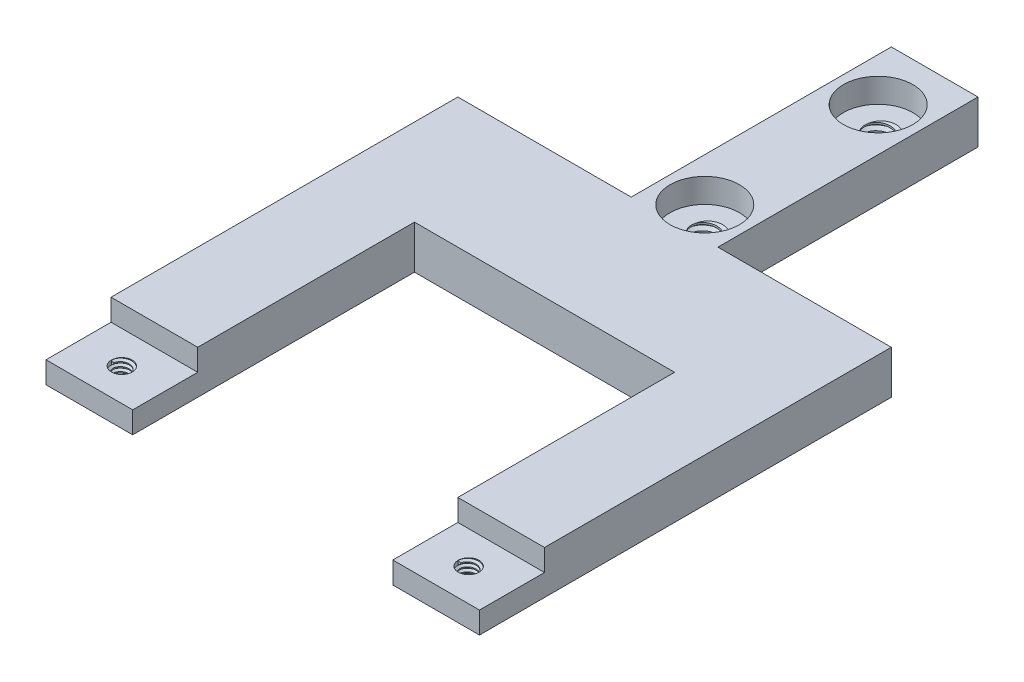
SolidWorks part; units mm, degrees
ref_plane "Front Plane" through (0, 0, 0) normal (0, 0, 1) x (1, 0, 0)
ref_plane "Top Plane" through (0, 0, 0) normal (0, 1, 0) x (1, 0, 0)
ref_plane "Right Plane" through (0, 0, 0) normal (1, 0, 0) x (0, 0, -1)
sketch "Sketch1" plane through (0, 0, 0) normal (0, 1, 0) x (1, 0, 0)
  line L1 (-15.875, 15.0812) -> (15.875, 15.0812)
  line L2 (-15.875, 15.0812) -> (-15.875, -15.0812)
  line L3 (-15.875, -15.0812) -> (15.875, -15.0812)
  line L4 (15.875, 15.0812) -> (15.875, -15.0812)
  line L5 (-9.525, -15.0812) -> (9.525, -15.0812)
  line L6 (-9.525, -15.0812) -> (-9.525, 5.5562)
  line L7 (-9.525, 5.5562) -> (9.525, 5.5562)
  line L8 (9.525, -15.0812) -> (9.525, 5.5562)
  line L9 (-3.175, 15.0813) -> (3.175, 15.0813)
  line L10 (-3.175, 15.0813) -> (-3.175, 34.1313)
  line L11 (-3.175, 34.1313) -> (3.175, 34.1313)
  line L12 (3.175, 15.0813) -> (3.175, 34.1313)
  point P4 (0, 15.0813)
  point P6 (-15.875, 0)
  point P11 (0, 5.5563)
  point P16 (0, 15.0813)
  dimension "D1" = 31.75
  dimension "D2" = 30.1625
  dimension "D3" = 6.35
  dimension "D4" = 9.525
  dimension "D5" = 6.35
  dimension "D6" = 19.05
extrude "Boss-Extrude1" add sketch "Sketch1" along normal mid plane 3.175 contours L8 L3 L4 L1 L2 L6 L7 | L10 L9 L12 L11 region at (-9.525, 0, -14.6433)
sketch "Sketch2" plane through (0, 1.5875, 0) normal (0, 1, 0) x (1, 0, 0)
  line L0 (-9.525, -15.0812) -> (-9.525, 5.5562) construction
  line L1 (-15.875, -15.0812) -> (-9.525, -15.0812)
  line L2 (-15.875, -15.0812) -> (-15.875, -10.3187)
  line L3 (-15.875, -10.3187) -> (-9.525, -10.3187)
  line L4 (-9.525, -15.0812) -> (-9.525, -10.3187)
  line L5 (15.875, 15.0812) -> (15.875, -15.0812) construction
  line L6 (9.525, -15.0812) -> (15.875, -15.0812)
  line L7 (9.525, -15.0812) -> (9.525, -10.3187)
  line L8 (9.525, -10.3187) -> (15.875, -10.3187)
  line L9 (15.875, -15.0812) -> (15.875, -10.3187)
  dimension "D1" = 4.7625
extrude "Cut-Extrude1" cut sketch "Sketch2" against normal blind 1.5875
sketch "Sketch3" plane through (0, 1.5875, 0) normal (0, 1, 0) x (1, 0, 0)
  line L0 (-9.525, -10.3187) -> (-15.875, -10.3187) construction
  line L1 (-15.875, -10.3187) -> (-15.875, -15.0812) construction
  line L2 (0, -1000) -> (0, 49000) construction
  line L5 (-3.175, 34.1313) -> (3.175, 34.1313) construction
  circle A0 centre (-12.7, -12.7) radius 0.762
  circle A2 centre (12.7, -12.7) radius 0.762
  circle A4 centre (0, 17.294) radius 1.2573
  circle A5 centre (0, 29.994) radius 1.2573
  point P6 (-12.7, -10.3187)
  point P9 (-15.875, -12.7)
  dimension "D1" = 2.5146
  dimension "D2" = 1.524
  dimension "D5" = 12.7
  dimension "D6" = 4.1372
extrude "Cut-Extrude2" cut sketch "Sketch3" against normal up to surface (3.175 mm away) from surface up to face at (0, -1.5875, -6.6146) starting at face at (0, 1.5875, -8.2021)
thread "Thread8" pitch 0.3175 method extrude profile "Thread Profile9" start angle 0, offset 0, length 0, pitch 0.3175, diameter 1.524
ref_plane "Plane9" through (-13.462, 0, 12.7) normal (0, 0, 1) x (-1, 0, 0)
sketch "Thread Profile9" plane through (-13.462, 0, 12.7) normal (0, 0, 1) x (-1, 0, 0)
  line L0 (0, 0) -> (0, 0.3175) construction
  line L11 (0, 0) -> (0, 0.2778)
  line L12 (0, 0.2778) -> (-0.1719, 0.1786)
  line L13 (-0.1719, 0.1786) -> (-0.1719, 0.0992)
  line L15 (-0.1719, 0.0992) -> (0, 0)
  line L17 (-0.1719, 0.1389) -> (0, 0.1389) construction
  point P2 (0, 0)
  dimension "Pitch" = 0.3175
  dimension "Profile_Angle" = 60
  dimension "Profile_Land" = 0.0794
  dimension "Profile_Height" = 0.1719
thread "Thread9" pitch 0.3175 method extrude profile "Thread Profile10" start angle 0, offset 0, length 0, pitch 0.3175, diameter 1.524
ref_plane "Plane10" through (11.938, 0, 12.7) normal (0, 0, 1) x (-1, 0, 0)
sketch "Thread Profile10" plane through (11.938, 0, 12.7) normal (0, 0, 1) x (-1, 0, 0)
  line L0 (0, 0) -> (0, 0.3175) construction
  line L11 (0, 0) -> (0, 0.2778)
  line L12 (0, 0.2778) -> (-0.1719, 0.1786)
  line L13 (-0.1719, 0.1786) -> (-0.1719, 0.0992)
  line L15 (-0.1719, 0.0992) -> (0, 0)
  line L17 (-0.1719, 0.1389) -> (0, 0.1389) construction
  point P2 (0, 0)
  dimension "Pitch" = 0.3175
  dimension "Profile_Angle" = 60
  dimension "Profile_Land" = 0.0794
  dimension "Profile_Height" = 0.1719
sketch "Sketch25" plane through (-15.875, 0, 0) normal (-1, 0, 0) x (0, 0, 1)
  line L1 (-34.1313, -1.5875) -> (17.4266, -1.5875)
  line L2 (-34.1313, -1.5875) -> (-34.1313, -4.2188)
  line L3 (-34.1313, -4.2188) -> (17.4266, -4.2188)
  line L4 (17.4266, -1.5875) -> (17.4266, -4.2188)
extrude "Cut-Extrude4" cut sketch "Sketch25" against normal through all
thread "Thread10" pitch 0.5292 method extrude profile "Thread Profile11" start angle 0, offset 0, length 0, pitch 0.5292, diameter 2.5146
ref_plane "Plane11" through (-1.2573, 1.5875, -29.994) normal (0, 0, 1) x (-1, 0, 0)
sketch "Thread Profile11" plane through (-1.2573, 1.5875, -29.994) normal (0, 0, 1) x (-1, 0, 0)
  line L0 (0, 0) -> (0, 0.5292) construction
  line L11 (0, 0) -> (0, 0.463)
  line L12 (0, 0.463) -> (-0.2864, 0.2977)
  line L13 (-0.2864, 0.2977) -> (-0.2864, 0.1654)
  line L15 (-0.2864, 0.1654) -> (0, 0)
  line L17 (-0.2864, 0.2315) -> (0, 0.2315) construction
  point P2 (0, 0)
  dimension "Pitch" = 0.5292
  dimension "Profile_Angle" = 60
  dimension "Profile_Land" = 0.1323
  dimension "Profile_Height" = 0.2864
thread "Thread11" pitch 0.5292 method extrude profile "Thread Profile12" start angle 0, offset 0, length 0, pitch 0.5292, diameter 2.5146
ref_plane "Plane12" through (-1.2573, 1.5875, -17.294) normal (0, 0, 1) x (-1, 0, 0)
sketch "Thread Profile12" plane through (-1.2573, 1.5875, -17.294) normal (0, 0, 1) x (-1, 0, 0)
  line L0 (0, 0) -> (0, 0.5292) construction
  line L11 (0, 0) -> (0, 0.463)
  line L12 (0, 0.463) -> (-0.2864, 0.2977)
  line L13 (-0.2864, 0.2977) -> (-0.2864, 0.1654)
  line L15 (-0.2864, 0.1654) -> (0, 0)
  line L17 (-0.2864, 0.2315) -> (0, 0.2315) construction
  point P2 (0, 0)
  dimension "Pitch" = 0.5292
  dimension "Profile_Angle" = 60
  dimension "Profile_Land" = 0.1323
  dimension "Profile_Height" = 0.2864
sketch "Sketch31" plane through (0, 1.5875, 0) normal (0, 1, 0) x (1, 0, 0)
  circle A0 centre (0, 17.294) radius 2.54
  circle A1 centre (0, 29.994) radius 2.54
  dimension "D1" = 5.08
  dimension "D2" = 5.08
extrude "Cut-Extrude5" cut sketch "Sketch31" against normal blind 1.778 body kept at (-13.4623, 0.0002, 12.7)
